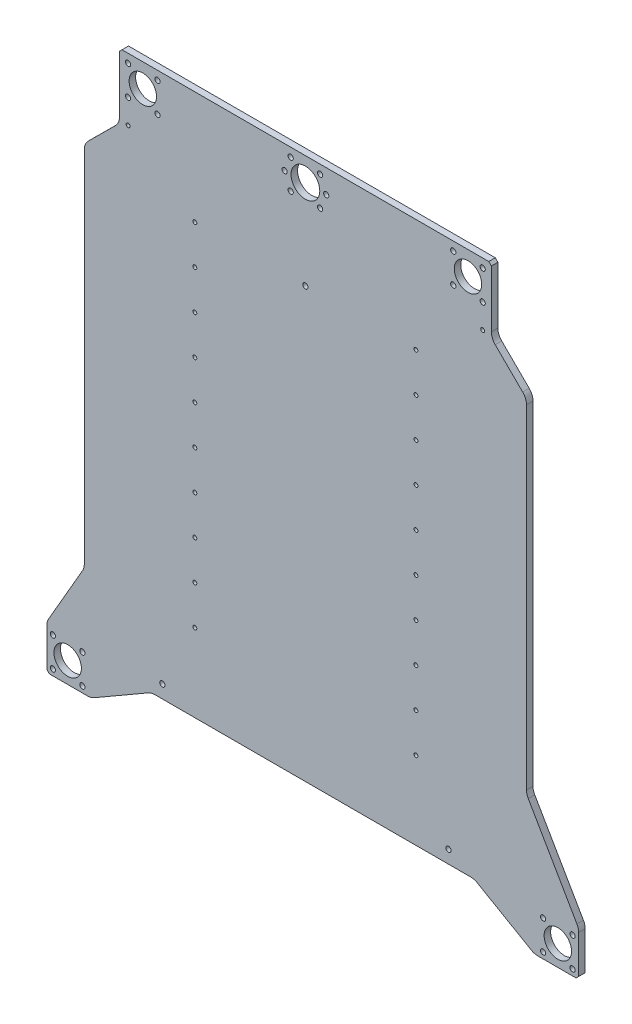
SolidWorks part; units mm, degrees
ref_plane "Front" through (0, 0, 0) normal (0, 0, 1) x (1, 0, 0)
ref_plane "Top" through (0, 0, 0) normal (0, 1, 0) x (1, 0, 0)
ref_plane "Right" through (0, 0, 0) normal (1, 0, 0) x (0, 0, -1)
sketch "Sketch1" plane through (0, 0, 0) normal (0, 0, 1) x (1, 0, 0)
  line L0 (50, 0) -> (-50, 0) construction
  line L1 (-170, -170) -> (0, -170)
  line L2 (-170, -170) -> (-170, 170)
  line L3 (-170, 170) -> (0, 170)
  line L4 (0, -170) -> (0, 170)
  line L5 (-170, -170) -> (0, 170) construction
  line L6 (-170, 170) -> (0, -170) construction
  line L7 (0, -50) -> (0, 50) construction
  point P0 (-85, 0)
  dimension "D1" = 340
  dimension "D2" = 170
extrude "Boss-Extrude1" add sketch "Sketch1" along normal blind 5
sketch "Sketch2" plane through (0, 0, 5) normal (0, 0, 1) x (1, 0, 0)
  line L0 (50, 0) -> (-50, 0) construction
  line L1 (-170, -170) -> (0, -170) construction
  line L2 (-170, -170) -> (-170, 170) construction
  line L3 (-170, 170) -> (0, 170) construction
  line L4 (0, -170) -> (0, 170) construction
  line L5 (-170, -170) -> (0, 170) construction
  line L6 (-170, 170) -> (0, -170) construction
  line L7 (0, -170) -> (0, 170) construction
  line L8 (-170, -170) -> (0, -170) construction
  line L9 (-110, -160) -> (-110, -170) construction
  line L10 (-170, 170) -> (-170, -170) construction
  circle A0 centre (-110, -160) radius 2
  circle A1 centre (0, 160) radius 2
  point P0 (-85, 0)
  dimension "D3" = 4
  dimension "D1" = 170
  dimension "D2" = 340
  dimension "D4" = 60
  dimension "D5" = 10
  dimension "D6" = 10
extrude "Cut-Extrude1" cut sketch "Sketch2" against normal through all
sketch "Sketch3" plane through (0, 0, 5) normal (0, 0, 1) x (1, 0, 0)
  line L0 (-170, 170) -> (-143, 196.8)
  line L1 (-143, 196.8) -> (-143, 246.8)
  line L2 (-143, 246.8) -> (0, 246.8)
  line L3 (0, 246.8) -> (0, 239.85)
  line L4 (0, 217.75) -> (0, 170)
  line L5 (0, 170) -> (-170, 170) construction
  line L6 (-16, 228.8) -> (0, 228.8) construction
  line L7 (0, 228.8) -> (-11.3137, 240.1137) construction
  line L8 (0, 228.8) -> (-11.3137, 217.4863) construction
  line L9 (-125, 228.8) -> (0, 228.8) construction
  line L10 (-21, 213.8) -> (21, 213.8) construction
  line L11 (-21, 213.8) -> (-21, 243.8) construction
  line L12 (-21, 243.8) -> (21, 243.8) construction
  line L13 (21, 213.8) -> (21, 243.8) construction
  line L14 (-21, 213.8) -> (21, 243.8) construction
  line L15 (-21, 243.8) -> (21, 213.8) construction
  line L16 (-141, 212.8) -> (-109, 212.8) construction
  line L17 (-141, 212.8) -> (-141, 244.8) construction
  line L18 (-141, 244.8) -> (-109, 244.8) construction
  line L19 (-109, 212.8) -> (-109, 244.8) construction
  line L20 (-141, 212.8) -> (-109, 244.8) construction
  line L21 (-141, 244.8) -> (-109, 212.8) construction
  line L22 (-170, 170) -> (0, 170)
  line L23 (-136.3137, 217.4863) -> (-136.3137, 198.8) construction
  arc A0 (0, 239.85) -> (0, 217.75) centre (0, 228.8) ccw
  circle A1 centre (0, 228.8) radius 16 construction
  circle A2 centre (-11.3137, 240.1137) radius 2
  circle A3 centre (-11.3137, 217.4863) radius 2
  circle A4 centre (-16, 228.8) radius 2
  circle A5 centre (-125, 228.8) radius 10.55
  circle A6 centre (-125, 228.8) radius 16 construction
  circle A7 centre (-136.3137, 240.1137) radius 2
  circle A8 centre (-113.6863, 240.1137) radius 2
  circle A9 centre (-136.3137, 217.4863) radius 2
  circle A10 centre (-113.6863, 217.4863) radius 2
  circle A11 centre (-136.3137, 198.8) radius 1.5
  point P23 (-125, 228.8)
  dimension "D3" = 4
  dimension "D4" = 32
  dimension "D2" = 11.05
  dimension "D9" = 32
  dimension "D10" = 21.1
  dimension "D14" = 4
  dimension "D19" = 3
  dimension "D1" = 58.8
  dimension "D5" = 45
  dimension "D6" = 45
  dimension "D7" = 30
  dimension "D8" = 42
  dimension "D11" = 32
  dimension "D12" = 32
  dimension "D13" = 125
  dimension "D15" = 2
  dimension "D16" = 2
  dimension "D17" = 50
  dimension "D18" = 2
extrude "Boss-Extrude2" add sketch "Sketch3" against normal up to surface (5 mm away) up to face at (-57, 53.3333, 0)
chamfer "Chamfer3" distance 5 angle 45 1 edges at (-170, -170, 2.5)
fillet "Fillet1" radius 10 2 edges at (-170, 170, 2.5) (-143, 196.8, 2.5)
chamfer "Chamfer2" distance 2 angle 45 1 edges at (-143, 246.8, 2.5)
mirror "Mirror2" about plane through (0, 0, 0) normal (1, 0, 0) of "Chamfer3", "Boss-Extrude1", "Cut-Extrude1", "Boss-Extrude2", "Fillet1", "Chamfer2"
sketch "Sketch5" plane through (0, 0, 5) normal (0, 0, 1) x (1, 0, 0)
  line L0 (-198.8, -162.75) -> (-198.8, -196.75)
  line L1 (-198.8, -164.75) -> (-166.8, -164.75) construction
  line L2 (-198.8, -164.75) -> (-198.8, -196.75) construction
  line L3 (-198.8, -196.75) -> (-166.8, -196.75) construction
  line L4 (-166.8, -164.75) -> (-166.8, -196.75) construction
  line L5 (-198.8, -164.75) -> (-166.8, -196.75) construction
  line L6 (-198.8, -196.75) -> (-166.8, -164.75) construction
  line L7 (-198.8, -196.75) -> (-164.8, -196.75)
  line L8 (-198.8, -162.75) -> (-170, -112.8669)
  line L9 (-170, 165.8361) -> (-170, -165) construction
  line L10 (-164.8, -196.75) -> (-118.4676, -170)
  line L11 (-165, -170) -> (165, -170) construction
  line L12 (-170, -112.8669) -> (-118.4676, -170)
  line L13 (176.1, -196.75) -> (210.1, -196.75)
  line L14 (178.1, -164.75) -> (210.1, -164.75) construction
  line L15 (178.1, -164.75) -> (178.1, -196.75) construction
  line L16 (178.1, -196.75) -> (210.1, -196.75) construction
  line L17 (210.1, -164.75) -> (210.1, -196.75) construction
  line L18 (178.1, -164.75) -> (210.1, -196.75) construction
  line L19 (178.1, -196.75) -> (210.1, -164.75) construction
  line L20 (210.1, -196.75) -> (210.1, -162.75)
  line L21 (210.1, -162.75) -> (170, -93.2948)
  line L22 (170, 165.8361) -> (170, -165) construction
  line L23 (176.1, -196.75) -> (129.7676, -170)
  line L24 (170, -93.2948) -> (129.7676, -170)
  circle A0 centre (-182.8, -180.75) radius 10.55
  circle A1 centre (-182.8, -180.75) radius 16 construction
  circle A2 centre (-194.1137, -169.4363) radius 2
  circle A3 centre (-171.4863, -169.4363) radius 2
  circle A4 centre (-171.4863, -192.0637) radius 2
  circle A5 centre (-194.1137, -192.0637) radius 2
  circle A6 centre (-125, 228.8) radius 10.55 construction
  circle A7 centre (194.1, -180.75) radius 10.55
  circle A8 centre (194.1, -180.75) radius 16 construction
  circle A9 centre (205.4137, -192.0637) radius 2
  circle A10 centre (205.4137, -169.4363) radius 2
  circle A11 centre (182.7863, -169.4363) radius 2
  circle A12 centre (182.7863, -192.0637) radius 2
  circle A13 centre (125, 228.8) radius 10.55 construction
  point P0 (-182.8, -180.75)
  point P21 (194.1, -180.75)
  dimension "D1" = 21.1
  dimension "D3" = 32
  dimension "D4" = 4
  dimension "D14" = 32
  dimension "D15" = 21.1
  dimension "D16" = 4
  dimension "D2" = 32
  dimension "D5" = 0
  dimension "D6" = 0
  dimension "D7" = 57.8
  dimension "D8" = 409.55
  dimension "D9" = 30
  dimension "D10" = 30
  dimension "D11" = 2
  dimension "D12" = 2
  dimension "D13" = 32
  dimension "D18" = 69.1
  dimension "D19" = 0
  dimension "D20" = 0
  dimension "D21" = 2
  dimension "D22" = 2
  dimension "D23" = 30
  dimension "D24" = 30
extrude "Boss-Extrude3" add sketch "Sketch5" against normal up to surface (5 mm away) up to face at (-11.05, 228.8, 0)
chamfer "Chamfer4" distance 2 angle 45 2 edges at (-198.8, -196.75, 2.5) (210.1, -196.75, 2.5)
fillet "Fillet2" radius 10 8 edges at (-170, -112.8669, 2.5) (-118.4676, -170, 2.5) (-164.8, -196.75, 2.5) (-198.8, -162.75, 2.5) (170, -93.2948, 2.5) (210.1, -162.75, 2.5) (176.1, -196.75, 2.5) (129.7676, -170, 2.5)
sketch "Sketch4" plane through (0, 0, 5) normal (0, 0, 1) x (1, 0, 0)
  line L0 (-85, -140) -> (-85, 160) construction
  line L1 (-85, 160) -> (0, 160) construction
  line L3 (-170, 165.8361) -> (-170, -110.1874) construction
  circle A0 centre (-85, 160) radius 1.5
  circle A1 centre (-85, 130) radius 1.5
  circle A2 centre (-85, 100) radius 1.5
  circle A3 centre (-85, 70) radius 1.5
  circle A4 centre (-85, 40) radius 1.5
  circle A5 centre (-85, 10) radius 1.5
  circle A6 centre (-85, -20) radius 1.5
  circle A7 centre (-85, -50) radius 1.5
  circle A8 centre (-85, -80) radius 1.5
  circle A9 centre (-85, -110) radius 1.5
  circle A11 centre (-85, -140) radius 1.5 [skipped]
  dimension "D1" = 3
  dimension "D2" = 300
  dimension "D4" = 85
  dimension "D3" = 11
extrude "Cut-Extrude2" cut sketch "Sketch4" against normal through all
mirror "Mirror3" about plane through (0, 0, 0) normal (1, 0, 0) of "Cut-Extrude2"
equation "\"table_bot_x\"= \"print_bed_x@print_bed.Assembly\""
equation "\"table_bot_y\"= \"print_bed_y@print_bed.Assembly\""
equation "\"table_bot_z\"= 5"
equation "\"glass_x\"= \"table_bot_x\""
equation "\"glass_y\"= \"table_bot_y\""
equation "\"M3_d\"= \"M3_d@print_bed.Assembly\""
equation "\"D1@Sketch1\"=\"table_bot_y\""
equation "\"D2@Sketch1\"= \"table_bot_x\" / 2"
equation "\"D1@Boss-Extrude1\" = \"table_bot_z\""
equation "\"D1@Sketch2\"= \"glass_x\" / 2"
equation "\"D2@Sketch2\"= \"glass_y\""
equation "\"ball_screw_d\"= 12"
equation "\"D2@Sketch3\"=\"ball_screw_nut_d_out\" / 2"
equation "\"M4_d\"= \"M4_d@print_bed.Assembly\""
equation "\"D6@Sketch3\"=\"D5@Sketch3\""
equation "\"ball_screw_nut_screws_d\"= 32"
equation "\"D4@Sketch3\"= \"ball_screw_nut_screws_d\""
equation "\"ball_screw_nut_d\"= 42"
equation "\"ball_screw_nut_b\"= 30"
equation "\"D7@Sketch3\"=\"ball_screw_nut_b\""
equation "\"linear_bearing_screws_d\"= 32"
equation "\"linear_bearing_d_out\"= 21.1"
equation "\"linear_bearing_b\"=32"
equation "\"D9@Sketch3\"=\"linear_bearing_screws_d\""
equation "\"D10@Sketch3\"=\"linear_bearing_d_out\""
equation "\"D3@Sketch3\"=\"M4_d\""
equation "\"D8@Sketch3\"=\"ball_screw_nut_d\""
equation "\"D11@Sketch3\"= \"linear_bearing_b\""
equation "\"D12@Sketch3\"=\"linear_bearing_b\""
equation "\"D14@Sketch3\"=\"M4_d\""
equation "\"rods_t\"= 250"
equation "\"D13@Sketch3\" = \"rods_t\" / 2"
equation "\"D15@Sketch3\"=\"D16@Sketch3\""
equation "\"ball_screw_nut_d_out\"= 22.1"
equation "\"D3@Sketch2\"=\"M4_d\""
equation "\"D1@Sketch4\"=\"M3_d\""
equation "\"D4@Sketch4\"=\"table_bot_x\" / 4"
equation "\"D1@Sketch5\"=\"linear_bearing_d_out\""
equation "\"D2@Sketch5\"=\"linear_bearing_b\""
equation "\"D3@Sketch5\"=\"linear_bearing_screws_d\""
equation "\"D4@Sketch5\"=\"M4_d\""
equation "\"D13@Sketch5\"=\"linear_bearing_b\""
equation "\"D14@Sketch5\"=\"linear_bearing_screws_d\""
equation "\"D15@Sketch5\"=\"linear_bearing_d_out\""
equation "\"D16@Sketch5\"=\"M4_d\""
